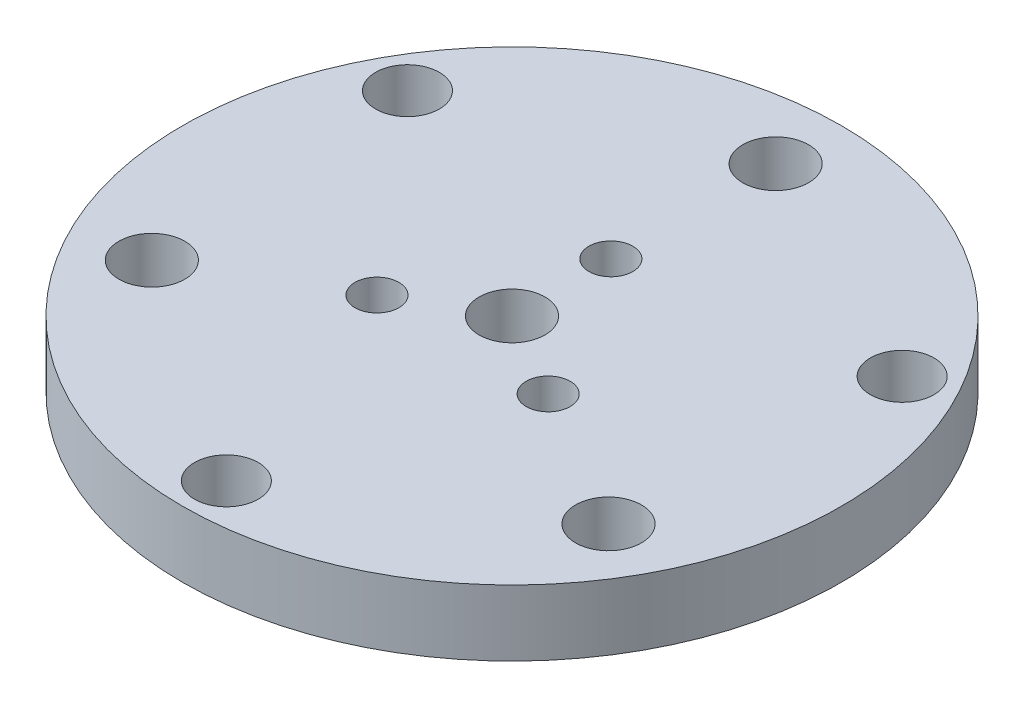
SolidWorks part; units mm, degrees
ref_plane "前视基准面" through (0, 0, 0) normal (0, 0, 1) x (1, 0, 0)
ref_plane "上视基准面" through (0, 0, 0) normal (0, 1, 0) x (1, 0, 0)
ref_plane "右视基准面" through (0, 0, 0) normal (1, 0, 0) x (0, 0, -1)
sketch "草图1" plane through (0, 0, 0) normal (0, 1, 0) x (1, 0, 0)
  line L0 (0, 0) -> (0, -22.4696) construction
  line L1 (0, 0) -> (23.0522, 0) construction
  circle A0 centre (0, 0) radius 13 construction
  circle A1 centre (0, 0) radius 12 construction
  circle A2 centre (0, -13) radius 1.45
  circle A3 centre (-11.2583, 6.5) radius 1.45
  circle A4 centre (11.2583, 6.5) radius 1.45
  circle A5 centre (0, 12) radius 1.5
  circle A6 centre (10.3923, -6) radius 1.5
  circle A7 centre (-10.3923, -6) radius 1.5
  circle A9 centre (0, 0) radius 15
  circle A10 centre (0, 0) radius 4.5 construction
  circle A11 centre (0, 4.5) radius 1
  circle A12 centre (3.8971, -2.25) radius 1
  circle A13 centre (-3.8971, -2.25) radius 1
  circle A14 centre (0, 0) radius 1.5
  point P16 (0, 0)
  point P23 (0, 0)
  point P32 (0, 0)
  dimension "D1" = 26
  dimension "D2" = 24
  dimension "D3" = 2.9
  dimension "D5" = 3
  dimension "D7" = 9
  dimension "D8" = 30
  dimension "D9" = 2
  dimension "D4" = 3
  dimension "D6" = 3
  dimension "D10" = 3
extrude "凸台-拉伸1" add sketch "草图1" along normal blind 3
